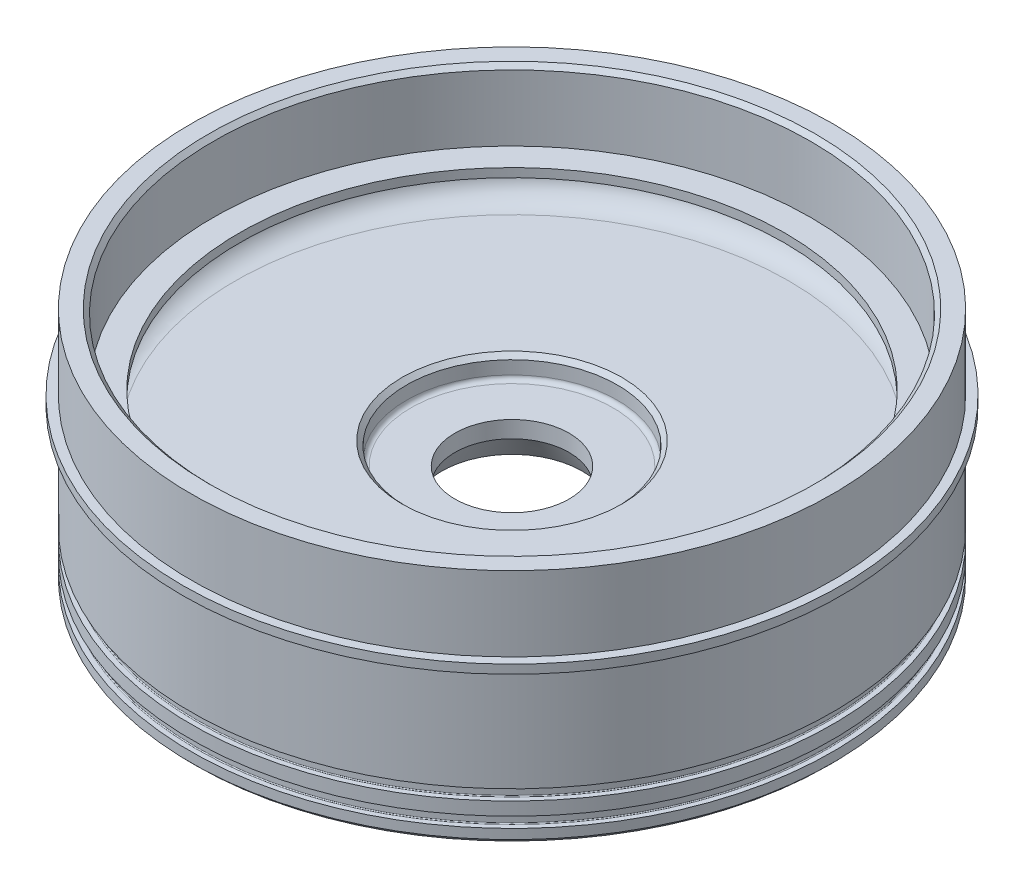
SolidWorks part; units mm, degrees
material "6061-T6 (SS)"
ref_plane "Piano frontale" through (0, 0, 0) normal (0, 0, 1) x (1, 0, 0)
ref_plane "Piano superiore" through (0, 0, 0) normal (0, 1, 0) x (1, 0, 0)
ref_plane "Piano destro" through (0, 0, 0) normal (1, 0, 0) x (0, 0, -1)
sketch "Schizzo1" plane through (0, 0, 0) normal (0, 0, 1) x (1, 0, 0)
  line L0 (0, 0) -> (0, 25.5769) construction
  line L1 (-13, 0) -> (-73, 0)
  line L2 (-73, 0) -> (-73, 14)
  line L3 (-73, 14) -> (-24, 14)
  line L4 (-24, 14) -> (-24, 9)
  line L5 (-24, 9) -> (-13, 9)
  line L6 (-13, 9) -> (-13, 0)
  line L7 (-24, 14) -> (-13, 14)
  line L8 (-13, 14) -> (-13, 9)
  line L9 (-73, 14) -> (-73, 40)
  line L10 (-73, 40) -> (-68, 40)
  line L11 (-69, 0) -> (-69, -14)
  line L12 (-69, -14) -> (-73, -14)
  line L13 (-73, -14) -> (-73, 0)
  line L14 (-68, 14) -> (-68, 40)
  line L15 (-73, 23) -> (-75, 23)
  line L16 (-75, 23) -> (-75, 21)
  line L17 (-73, -14) -> (-73, 0)
  line L18 (-73, -3) -> (-71.7, -3)
  line L19 (-71.7, -3) -> (-71.7, -5.4)
  line L20 (-71.7, -5.4) -> (-73, -5.4)
  line L21 (-73, -8.4) -> (-71.7, -8.4)
  line L22 (-71.7, -8.4) -> (-71.7, -10.8)
  line L23 (-71.7, -10.8) -> (-73, -10.8)
  line L24 (-75, 21) -> (-73, 21)
  line L25 (-68, 24) -> (-62, 24)
  line L26 (-62, 24) -> (-62, 22)
  line L27 (-62, 22) -> (-68, 22)
  dimension "D1" = 5
  dimension "D2" = 146
  dimension "D3" = 26
  dimension "D4" = 48
  dimension "D5" = 14
  dimension "D6" = 4
  dimension "D7" = 2.4
  dimension "D8" = 1.3
  dimension "D9" = 3
  dimension "D10" = 3
  dimension "D11" = 14
  dimension "D12" = 26
  dimension "D13" = 136
  dimension "D14" = 2
  dimension "D15" = 150
  dimension "D16" = 35
  dimension "D17" = 2
  dimension "D18" = 124
  dimension "D19" = 16
revolve "Rivoluzione1" add sketch "Schizzo1" angle 360 about L0 region at (-44.7166, 6.6847, 0) region at (-70.8307, -7.0125, 0) region at (-18.5, 11.5, 0) region at (-70.5, 27, 0) region at (-74, 22, 0) region at (-65, 23, 0)
chamfer "Smusso1" distance 3 angle 60 1 edges at (0, 0, -13) first distance on face at (0, 0, -69)
chamfer "Smusso2" distance 1 angle 45 1 edges at (0, -14, -69)
fillet "Raccordo1" radius 26 1 edges at (0, 0, -69)
chamfer "Smusso3" distance 1 angle 45 1 edges at (0, 40, -68)
fillet "Raccordo2" radius 0.2 4 edges at (0, -8.4, -71.7) (0, -10.8, -71.7) (0, -3, -71.7) (0, -5.4, -71.7)
sketch "Schizzo2" plane through (0, 0, 0) normal (0, 0, 1) x (1, 0, 0)
  line L0 (0, 0) -> (0, 58.1242) construction
  line L1 (0, 0) -> (-27.2443, 0) construction
  line L2 (-46.4833, 0) -> (46.4833, 0) construction
  line L3 (-13, 9) -> (-24, 9)
  line L4 (-24, 9) -> (-24, 14)
  line L6 (-24, 14) -> (-13, 14)
  line L7 (13, 14) -> (-13, 14) construction
  line L8 (-13, 14) -> (-13, 9)
  line L9 (-13, 9) -> (-13, 0) construction
  dimension "D1" = 5
  dimension "D2" = 48
revolve "Taglia-Rivoluzione1" cut sketch "Schizzo2" angle 360 about L0
fillet "Raccordo3" radius 1 1 edges at (0, 9, -24)
chamfer "Smusso4" distance 1 angle 45 1 edges at (0, 14, -24)
fillet "Raccordo4" radius 5 1 edges at (0, 14, -68)
chamfer "Smusso5" distance 1 angle 45 1 edges at (0, -14, -73)
